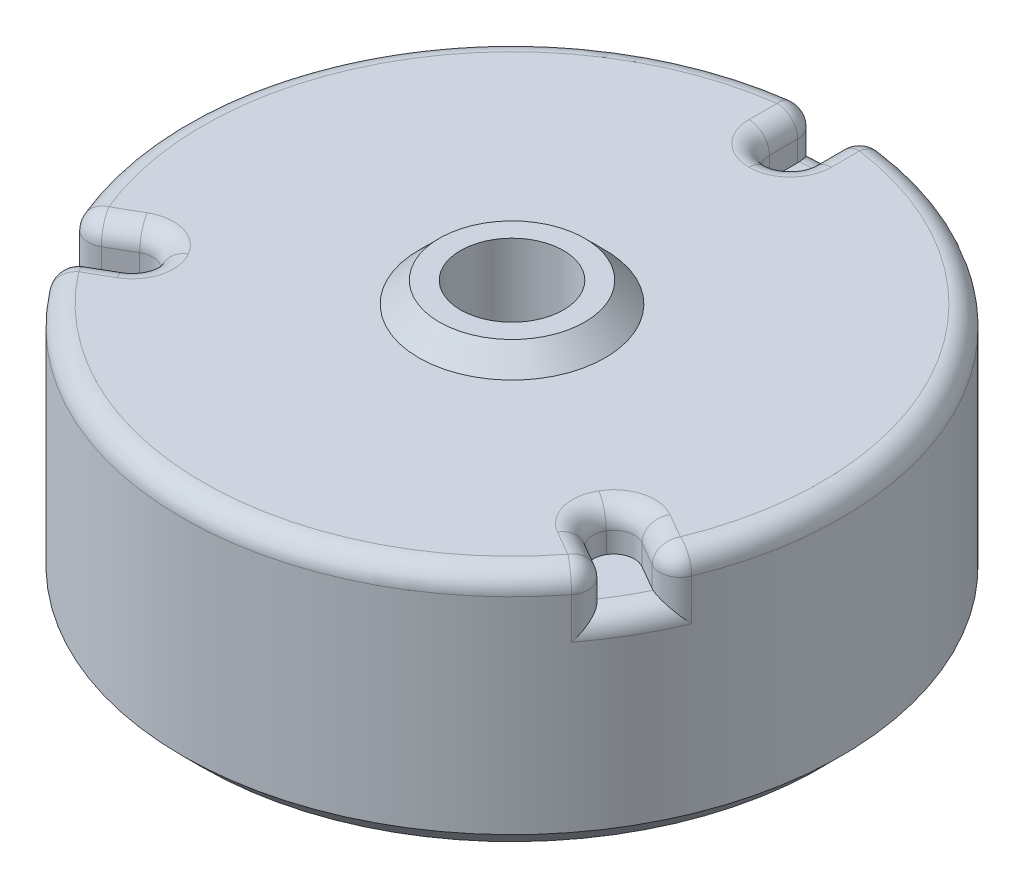
SolidWorks part; units mm, degrees
ref_plane "前视基准面" through (0, 0, 0) normal (0, 0, 1) x (1, 0, 0)
ref_plane "上视基准面" through (0, 0, 0) normal (0, 1, 0) x (1, 0, 0)
ref_plane "右视基准面" through (0, 0, 0) normal (1, 0, 0) x (0, 0, -1)
sketch "草图1" plane through (0, 0, 0) normal (0, 1, 0) x (1, 0, 0)
  circle A0 centre (0, 0) radius 12.5
  circle A1 centre (0, 0) radius 80
  dimension "D1" = 25
  dimension "D2" = 160
extrude "凸台-拉伸1" add sketch "草图1" along normal blind 60
sketch "草图2" plane through (0, 60, 0) normal (0, 1, 0) x (1, 0, 0)
  circle A0 centre (0, 0) radius 12.5
  circle A1 centre (0, 0) radius 22.6379
extrude "凸台-拉伸2" add sketch "草图2" along normal blind 5
chamfer "倒角1" distance 5 angle 45 1 edges at (0, 65, 22.6379)
chamfer "倒角2" distance 5 angle 45 1 edges at (0, 0, 80)
sketch "草图3" plane through (0, 60, 0) normal (0, 1, 0) x (1, 0, 0)
  line L1 (-5, 97.5) -> (5, 97.5)
  line L2 (-5, 97.5) -> (-5, 62.5)
  line L3 (-5, 62.5) -> (5, 62.5)
  line L4 (5, 97.5) -> (5, 62.5)
  line L5 (-5, 97.5) -> (5, 62.5) construction
  line L6 (-5, 62.5) -> (5, 97.5) construction
  circle A0 centre (0, 0) radius 80 construction
  point P0 (0, 80)
  dimension "D1" = 10
  dimension "D2" = 35
extrude "切除-拉伸1" cut sketch "草图3" against normal blind 10 contours L4 L3 L2 L1
fillet "圆角1" radius 5 5 edges at (0, 50, -80) (5, 55, -79.8436) (-5, 55, -79.8436) (5, 55, -62.5) (-5, 55, -62.5)
pattern_circular "阵列(圆周)1" count 3 over 360 about axis through (0, 60, 0) along (0, 1, 0) of "圆角1", "切除-拉伸1"
fillet "圆角2" radius 5 21 edges at (-6.7086, 60, -78.0942) (-5, 60, -70.9152) (-3.5355, 60, -63.9645) (3.5355, 60, -63.9645) (5, 60, -70.9152) (6.7086, 60, -78.0942) (69.282, 60, -40) (70.9859, 60, 33.2373) (63.9143, 60, 31.1275) (57.1626, 60, 28.9204) (53.6271, 60, 35.0441) (58.9143, 60, 39.7877) (64.2773, 60, 44.8569) (0, 60, 80) (-64.2773, 60, 44.8569) (-58.9143, 60, 39.7877) (-53.6271, 60, 35.0441) (-57.1626, 60, 28.9204) (-63.9143, 60, 31.1275) (-70.9859, 60, 33.2373) (-69.282, 60, -40)
